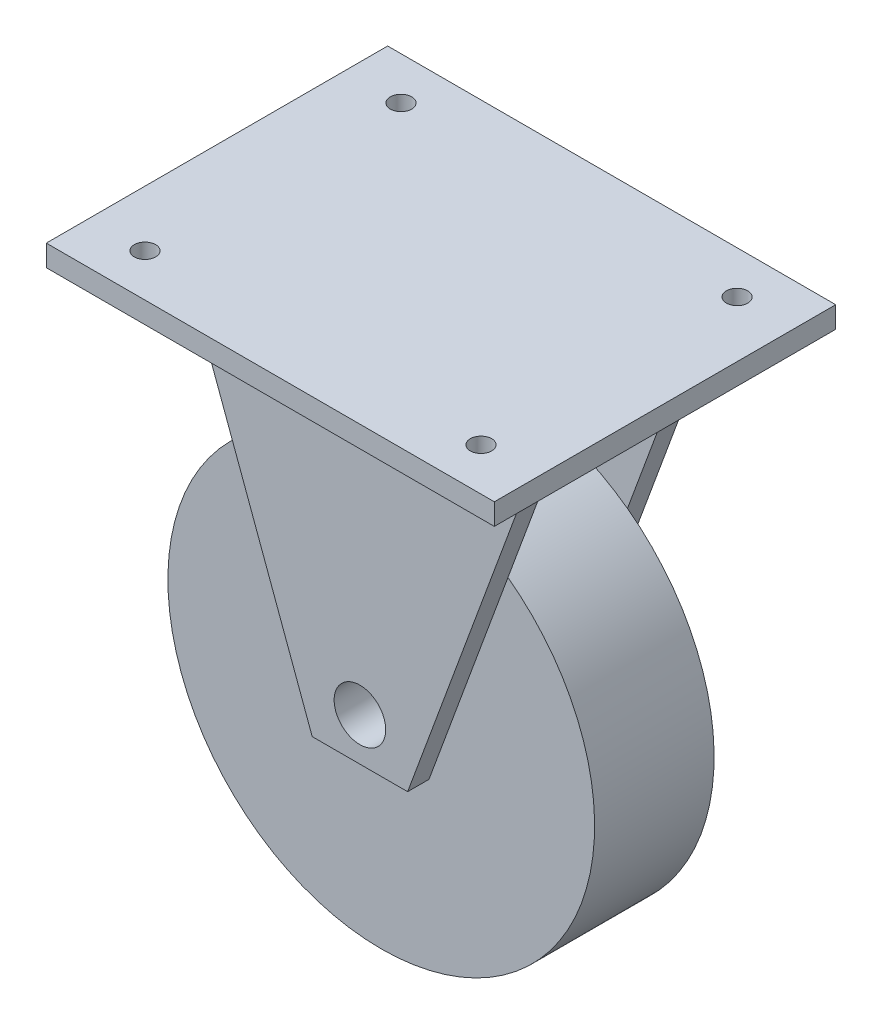
SolidWorks part; units mm, degrees
ref_plane "Спереди" through (0, 0, 0) normal (0, 0, 1) x (1, 0, 0)
ref_plane "Сверху" through (0, 0, 0) normal (0, 1, 0) x (1, 0, 0)
ref_plane "Справа" through (0, 0, 0) normal (1, 0, 0) x (0, 0, -1)
sketch "Эскиз1" plane through (0, 0, 0) normal (0, 1, 0) x (1, 0, 0)
  line L1 (-52.5, -40) -> (52.5, -40)
  line L2 (-52.5, -40) -> (-52.5, 40)
  line L3 (-52.5, 40) -> (52.5, 40)
  line L4 (52.5, -40) -> (52.5, 40)
  line L5 (-52.5, -40) -> (52.5, 40) construction
  line L6 (-52.5, 40) -> (52.5, -40) construction
  circle A0 centre (-39.375, 30) radius 2.5
  circle A1 centre (39.375, 30) radius 2.5
  circle A2 centre (39.375, -30) radius 2.5
  circle A3 centre (-39.375, -30) radius 2.5
  point P0 (0, 0)
  dimension "D3" = 60
  dimension "D4" = 5
  dimension "D5" = 5
  dimension "D6" = 5
  dimension "D7" = 5
  dimension "D1" = 105
  dimension "D2" = 80
extrude "Бобышка-Вытянуть1" add sketch "Эскиз1" along normal blind 5
sketch "Эскиз2" plane through (0, 0, 0) normal (0, 0, 1) x (1, 0, 0)
  line L2 (-46.046, -125) -> (131.9496, -125) construction
  line L3 (-52.5, 5) -> (52.5, 5) construction
  circle A0 centre (0, -75) radius 50
  point P4 (0, 0)
  dimension "D1" = 100
  dimension "D3" = 130
extrude "Бобышка-Вытянуть2" add sketch "Эскиз2" along normal blind 28 from offset 14 separate body offset against normal yes
sketch "Эскиз3" plane through (0, 0, 14) normal (0, 0, 1) x (1, 0, 0)
  line L0 (-11.1803, -85) -> (11.1803, -85)
  line L1 (11.1803, -85) -> (42.5, 0)
  line L2 (-52.5, 0) -> (52.5, 0) construction
  line L3 (42.5, 0) -> (-42.5, 0)
  line L4 (-42.5, 0) -> (-11.1803, -85)
  line L5 (-50, -75) -> (50, -75) construction
  circle A0 centre (0, -75) radius 50 construction
  point P13 (0, -75)
  dimension "D1" = 10
  dimension "D2" = 10
  dimension "D3" = 10
  dimension "D4" = 15
  dimension "D5" = 15
extrude "Бобышка-Вытянуть3" add sketch "Эскиз3" along normal blind 5
pattern_linear "Линейный массив1" count 2 spacing 33 along (0, 0, -1) of "Бобышка-Вытянуть3"
sketch "Эскиз4" plane through (0, 0, -19) normal (0, 0, -1) x (-1, 0, 0)
  circle A0 centre (0, -75) radius 6.0449
extrude "Вырез-Вытянуть1" cut sketch "Эскиз4" against normal through all
